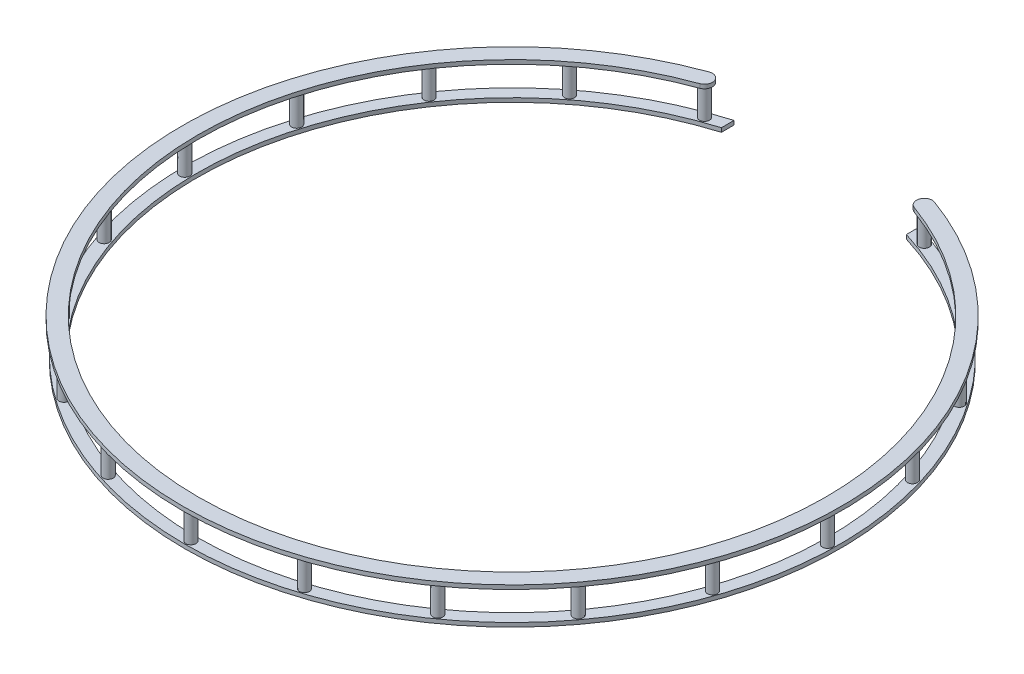
SolidWorks part; units mm, degrees
ref_plane "Front Plane" through (0, 0, 0) normal (0, 0, 1) x (1, 0, 0)
ref_plane "Top Plane" through (0, 0, 0) normal (0, 1, 0) x (1, 0, 0)
ref_plane "Right Plane" through (0, 0, 0) normal (1, 0, 0) x (0, 0, -1)
sketch "Sketch1" plane through (0, 0, 0) normal (0, 1, 0) x (1, 0, 0)
  circle A0 centre (0, 0) radius 7830.5409
  circle A1 centre (0, 0) radius 8130.5409
  dimension "D1" = 15661.0818
  dimension "D2" = 300
extrude "Boss-Extrude1" add sketch "Sketch1" along normal blind 100
sketch "Sketch2" plane through (0, 100, 0) normal (0, 1, 0) x (1, 0, 0)
  line L1 (-1850, 8833.8276) -> (1850, 8833.8276)
  line L2 (-1850, 8833.8276) -> (-1850, 6827.2542)
  line L3 (-1850, 6827.2542) -> (1850, 6827.2542)
  line L4 (1850, 8833.8276) -> (1850, 6827.2542)
  line L5 (-1850, 8833.8276) -> (1850, 6827.2542) construction
  line L6 (-1850, 6827.2542) -> (1850, 8833.8276) construction
  circle A0 centre (0, 0) radius 7830.5409 construction
  point P0 (0, 7830.5409)
  dimension "D1" = 3700
extrude "Cut-Extrude1" cut sketch "Sketch2" against normal blind 100 and the other way blind 100
sketch "Sketch4" plane through (0, 100, 0) normal (0, 1, 0) x (1, 0, 0)
  line L0 (0, -7830.5409) -> (0, -8130.5409) construction
  arc A0 (-1850, 7608.8679) -> (1850, 7608.8679) centre (0, 0) ccw construction
  arc A1 (-1850, 7917.272) -> (1850, 7917.272) centre (0, 0) ccw construction
  circle A2 centre (0, -7980.5409) radius 125
  dimension "D1" = 250
extrude "Boss-Extrude2" add sketch "Sketch4" along normal blind 750
pattern_circular "CirPattern1" count 10 every 17.778 about axis through (0, 100, 0) along (0, 1, 0) of "Boss-Extrude2" other way count 10
ref_plane "Plane2" through (0, 850, 0) normal (0, 1, 0) x (1, 0, 0)
sketch "Sketch5" plane through (0, 850, 0) normal (0, 1, 0) x (1, 0, 0)
  arc A0 (-2729.5057, 7499.2554) -> (2729.5057, 7499.2554) centre (0, -7.4092) ccw construction
  arc A1 (-2796.4047, 7683.2403) -> (2796.4047, 7683.2403) centre (0, -7.4092) ccw
  arc A2 (-2662.6068, 7315.2705) -> (2662.6068, 7315.2705) centre (0, -7.4092) ccw
  arc A3 (-2662.6068, 7315.2705) -> (-2796.4047, 7683.2403) centre (-2729.5057, 7499.2554) ccw
  arc A4 (2796.4047, 7683.2403) -> (2662.6068, 7315.2705) centre (2729.5057, 7499.2554) ccw
  point P3 (0, -7994.9128)
extrude "Boss-Extrude3" add sketch "Sketch5" along normal blind 100
sketch "Sketch6" plane through (0, 100, 0) normal (0, 1, 0) x (1, 0, 0)
  line L1 (-2296.3939, 8137.3759) -> (2296.3939, 8137.3759)
  line L2 (-2296.3939, 8137.3759) -> (-2296.3939, 7404.2483)
  line L3 (-2296.3939, 7404.2483) -> (2296.3939, 7404.2483)
  line L4 (2296.3939, 8137.3759) -> (2296.3939, 7404.2483)
  line L5 (-2296.3939, 8137.3759) -> (2296.3939, 7404.2483) construction
  line L6 (-2296.3939, 7404.2483) -> (2296.3939, 8137.3759) construction
  point P0 (0, 7770.8121)
extrude "Cut-Extrude2" cut sketch "Sketch6" against normal blind 2000 and the other way blind 2000
sketch "Sketch7" plane through (0, 100, 0) normal (0, 1, 0) x (1, 0, 0)
  line L0 (-2296.3939, 7799.5045) -> (2296.3939, 7799.5045) construction
